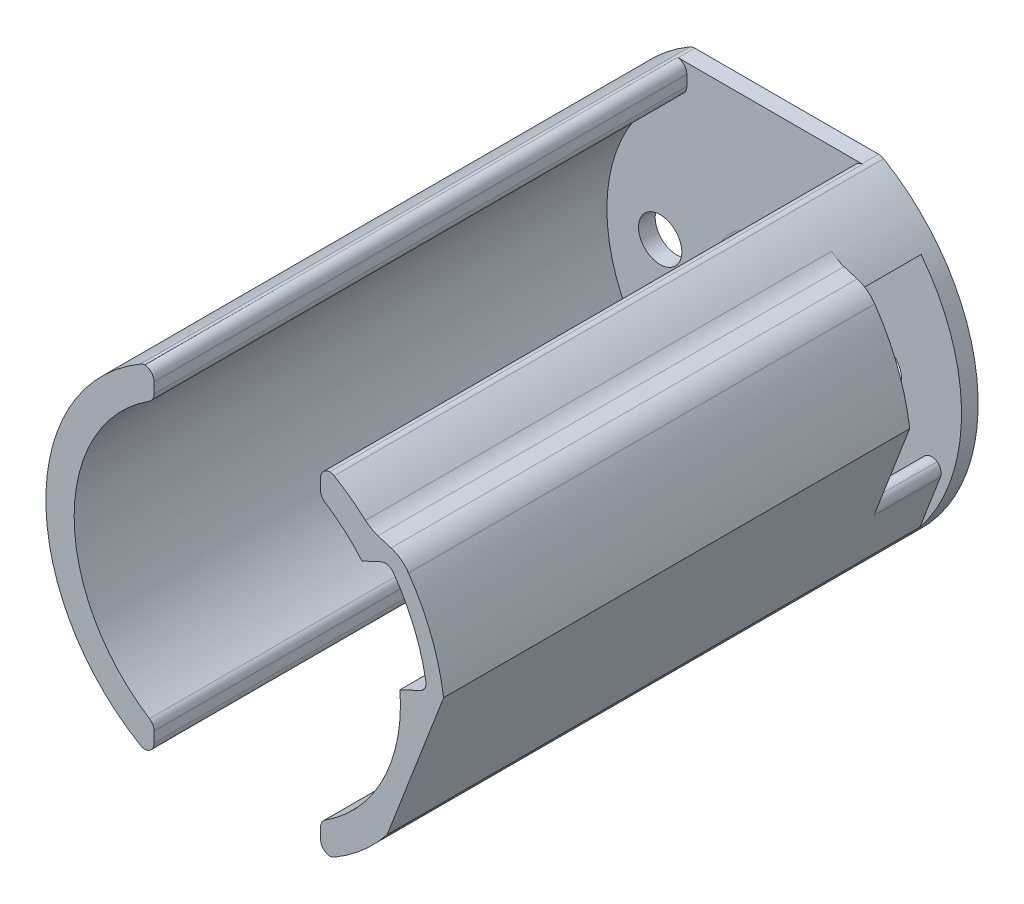
SolidWorks part; units mm, degrees
ref_plane "Front Plane" through (0, 0, 0) normal (0, 0, 1) x (1, 0, 0)
ref_plane "Top Plane" through (0, 0, 0) normal (0, 1, 0) x (1, 0, 0)
ref_plane "Right Plane" through (0, 0, 0) normal (1, 0, 0) x (0, 0, -1)
sketch "Sketch1" plane through (0, 0, 0) normal (0, 0, 1) x (1, 0, 0)
  circle A0 centre (0, 0) radius 12.446
  circle A1 centre (0, 0) radius 14.605
  dimension "D1" = 24.892
  dimension "D2" = 29.21
extrude "Boss-Extrude1" add sketch "Sketch1" along normal blind 40.64
sketch "Sketch2" plane through (0, 0, 0) normal (0, 0, -1) x (-1, 0, 0)
  circle A0 centre (0, 0) radius 14.605
  circle A1 centre (0, 0) radius 3.556
  circle A2 centre (-8.382, 0) radius 1.651
  circle A3 centre (8.382, 0) radius 1.651
  dimension "D1" = 7.112
  dimension "D4" = 3.302
  dimension "D2" = 16.764
  dimension "D3" = 8.382
extrude "Boss-Extrude2" add sketch "Sketch2" along normal blind 1.27
sketch "Sketch3" plane through (0, 0, -1.27) normal (0, 0, -1) x (-1, 0, 0)
  line L1 (-16.4466, 19.1182) -> (17.6099, 19.1182)
  line L2 (-16.4466, 19.1182) -> (-16.4466, 12.7)
  line L3 (-16.4466, 12.7) -> (17.6099, 12.7)
  line L4 (17.6099, 19.1182) -> (17.6099, 12.7)
  line L5 (-16.4466, -18.2758) -> (18.5325, -18.2758)
  line L6 (-16.4466, -18.2758) -> (-16.4466, -12.7)
  line L7 (-16.4466, -12.7) -> (18.5325, -12.7)
  line L8 (18.5325, -18.2758) -> (18.5325, -12.7)
  dimension "D1" = 25.4
  dimension "D2" = 12.7
extrude "Cut-Extrude1" cut sketch "Sketch3" against normal through all
sketch "Sketch4" plane through (0, 12.7, 0) normal (0, 1, 0) x (1, 0, 0)
  line L0 (7.2122, 1.27) -> (-7.2122, 1.27) construction
  line L1 (-6.35, -40.64) -> (6.35, -40.64)
  line L2 (-6.35, -40.64) -> (-6.35, 0)
  line L3 (-6.35, 0) -> (6.35, 0)
  line L4 (6.35, -40.64) -> (6.35, 0)
  line L5 (7.2122, -40.64) -> (-7.2122, -40.64) construction
  dimension "D1" = 1.27
  dimension "D2" = 12.7
  dimension "D3" = 6.35
extrude "Cut-Extrude2" cut sketch "Sketch4" against normal through all
sketch "Sketch5" plane through (0, 0, 40.64) normal (0, 0, 1) x (1, 0, 0)
  line L1 (8.707, 7.6569) -> (15.1561, 10.6642)
  line L2 (8.707, 7.6569) -> (11.9273, 0.7509)
  line L3 (11.9273, 0.7509) -> (18.3764, 3.7582)
  line L4 (15.1561, 10.6642) -> (18.3764, 3.7582)
  dimension "D1" = 7.62
extrude "Cut-Extrude3" cut sketch "Sketch5" against normal up to surface (40.64 mm away) up to face at (0, 0, 0)
sketch "Sketch6" plane through (0, 0, -1.27) normal (0, 0, -1) x (-1, 0, 0)
  line L0 (0, 0) -> (-14.6385, 6.1425) construction
  line L4 (-12.5272, 9.7511) -> (-10.1697, 10.4826)
  line L5 (-15.7344, 2.1078) -> (-14.6047, -0.0869)
  arc A1 (-7.2122, 12.7) -> (-11.525, 8.971) centre (0, 0) ccw construction
  arc A2 (-12.5272, 9.7511) -> (-15.7344, 2.1078) centre (0, 0) ccw
  arc A3 (-12.5272, 9.7511) -> (-15.7344, 2.1078) centre (0, 0) ccw
  arc A4 (-14.4757, 1.9392) -> (-7.2122, -12.7) centre (0, 0) ccw construction
  arc A5 (-11.525, 8.971) -> (-14.4757, 1.9392) centre (0, 0) ccw construction
  arc A6 (-11.525, 8.971) -> (-14.4757, 1.9392) centre (0, 0) ccw
  arc A7 (-10.1697, 10.4826) -> (-11.525, 8.971) centre (0, 0) ccw
  arc A8 (-14.4757, 1.9392) -> (-14.6047, -0.0869) centre (0, 0) ccw
  dimension "D2" = 80
  dimension "D3" = 40
  dimension "D1" = 1.27
extrude "Boss-Extrude3" add sketch "Sketch6" against normal up to surface (41.91 mm away) up to face at (8.2483, 10.6901, 40.64)
sketch "Sketch7" plane through (0, 0, -1.27) normal (0, 0, -1) x (-1, 0, 0)
  circle A0 centre (0, 0) radius 14.605
  circle A1 centre (0, 0) radius 15.875
extrude "Cut-Extrude4" cut sketch "Sketch7" against normal blind 6.35
sketch "Sketch8" plane through (0, 0, 0) normal (0, 0, 1) x (1, 0, 0)
  line L0 (12.4078, 0.9749) -> (14.4757, 1.9392) construction
  line L1 (12.4078, 0.9749) -> (14.4757, 1.9392)
  line L2 (11.9313, -3.5423) -> (13.7807, -4.8373)
  line L3 (0, 0) -> (14.5494, -1.2729) construction
  arc A0 (6.35, -10.7042) -> (12.4078, 0.9749) centre (0, 0) ccw construction
  arc A1 (11.9313, -3.5423) -> (12.4078, 0.9749) centre (0, 0) ccw
  arc A2 (7.2122, -12.7) -> (14.6047, -0.0869) centre (0, 0) ccw construction
  arc A3 (13.7807, -4.8373) -> (14.4686, 1.9911) centre (0, 0) ccw
  arc M1 (6.35, -10.7042) -> (12.4078, 0.9749) centre (0, 0) ccw
  line M2 (12.4078, 0.9749) -> (14.4757, 1.9392)
  dimension "D1" = 60
  dimension "D2" = 30
extrude "Cut-Extrude5" cut sketch "Sketch8" along normal blind 5.08 contours A1 L3 A3 M2 | L3 L2 A3 M1
sketch "Sketch11" plane through (0, 0, 40.64) normal (0, 0, 1) x (1, 0, 0)
  line L0 (15.7344, 2.1078) -> (11.4289, -9.0932)
  line L1 (11.4289, -9.0932) -> (14.3925, -10.2323)
  line L2 (14.3925, -10.2323) -> (18.698, 0.9687)
  line L3 (18.698, 0.9687) -> (15.7344, 2.1078)
  line L4 (7.2122, -12.7) -> (20.3584, -12.7) construction
  arc A0 (7.2122, -12.7) -> (14.6047, -0.0869) centre (0, 0) ccw construction
  dimension "D1" = 12
  dimension "D2" = 3.175
extrude "Cut-Extrude6" cut sketch "Sketch11" against normal up to surface (40.64 mm away) up to face at (3.5999, 0.7096, 0)
sketch "Sketch12" plane through (0, 0, 40.64) normal (0, 0, 1) x (1, 0, 0)
  line L1 (14.577, -0.9032) -> (15.7344, 2.1078)
  line L2 (15.7344, 2.1078) -> (15.1557, 2.3303)
  line L3 (15.1557, 2.3303) -> (13.9983, -0.6807)
  line L4 (13.9983, -0.6807) -> (14.577, -0.9032)
extrude "Boss-Extrude5" add sketch "Sketch12" against normal up to surface (35.56 mm away)
fillet "Fillet1" radius 0.762 15 edges at (-3.556, 0, 0) (-7.2122, -12.7, 19.685) (-6.35, -12.7, 20.32) (-6.35, 10.7042, 20.32) (-6.35, -10.7042, 20.32) (6.35, -12.7, 20.32) (6.35, -10.7042, 20.32) (6.35, 10.7042, 20.32) (6.35, 12.7, 20.32) (-7.2122, 12.7, 19.685) (-6.35, 12.7, 20.32) (13.2166, -4.4423, 2.54) (11.9313, -3.5423, 2.54) (11.525, 8.971, 22.86) (14.4757, 1.9392, 22.86)
fillet "Fillet2" radius 2.54 2 edges at (12.5272, 9.7511, 22.86) (10.1697, 10.4826, 22.86)
equation "\"D3@Sketch4\"=\"D2@Sketch4\"/2"
